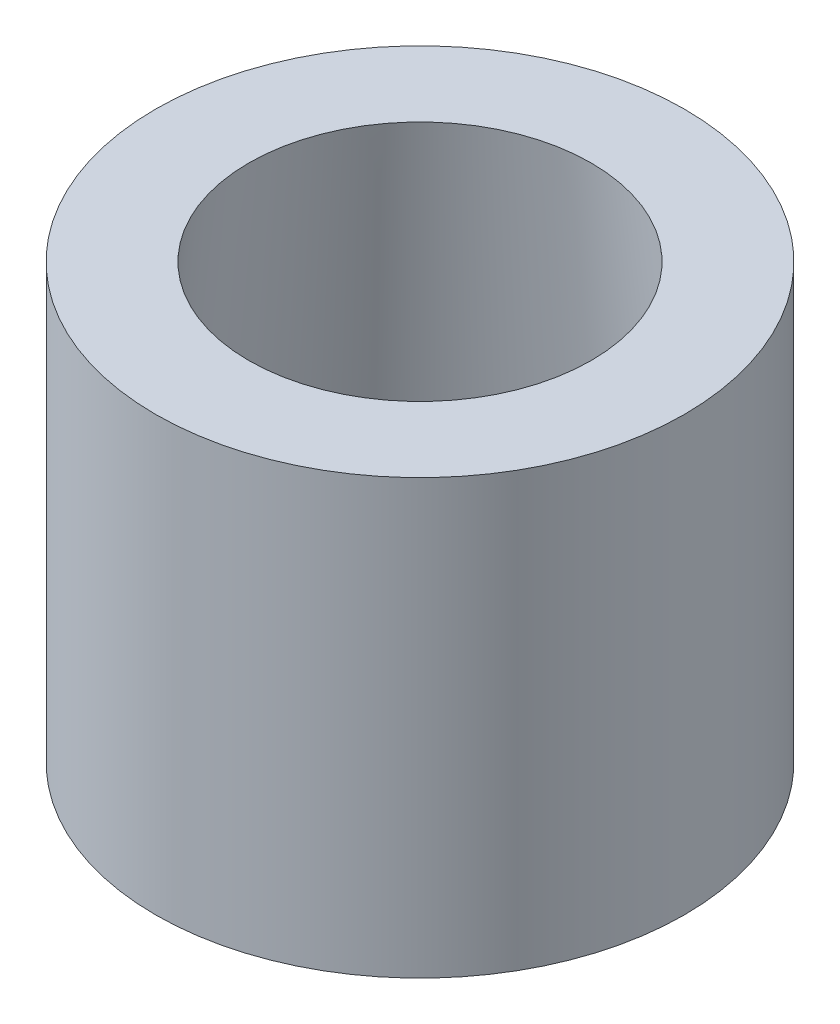
SolidWorks part; units mm, degrees
material "7075-T6 (SN)"
ref_plane "Front Plane" through (0, 0, 0) normal (0, 0, 1) x (1, 0, 0)
ref_plane "Top Plane" through (0, 0, 0) normal (0, 1, 0) x (1, 0, 0)
ref_plane "Right Plane" through (0, 0, 0) normal (1, 0, 0) x (0, 0, -1)
sketch "Sketch1" plane through (0, 0, 0) normal (0, 1, 0) x (1, 0, 0)
  circle A1 centre (0, 0) radius 30.5
extrude "Boss-Extrude1" add sketch "Sketch1" along normal blind 50
sketch "Sketch3" plane through (0, 0, 0) normal (0, -1, 0) x (-1, 0, 0)
  circle A0 centre (0, 0) radius 25
extrude "Cut-Extrude8" cut sketch "Sketch3" against normal through all draft 6
fillet "Fillet1" radius 4 1 edges at (0, 0, -25)
